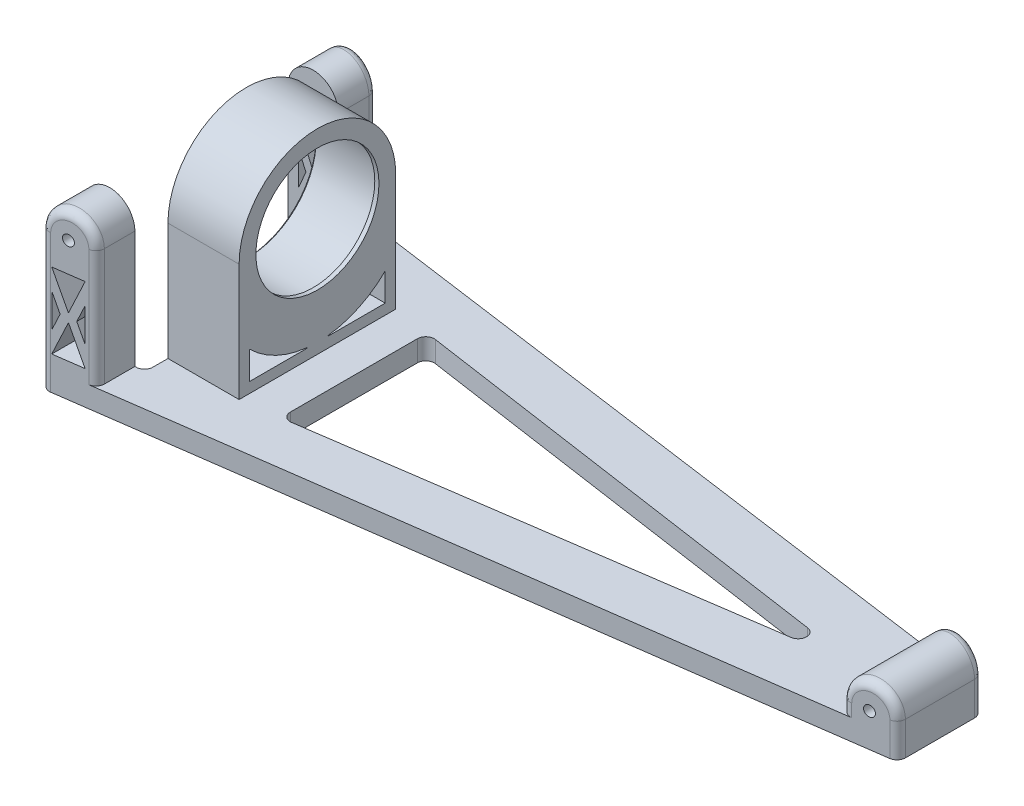
SolidWorks part; units mm, degrees
ref_plane "Front Plane" through (0, 0, 0) normal (0, 0, 1) x (1, 0, 0)
ref_plane "Top Plane" through (0, 0, 0) normal (0, 1, 0) x (1, 0, 0)
ref_plane "Right Plane" through (0, 0, 0) normal (1, 0, 0) x (0, 0, -1)
sketch "Sketch1" plane through (0, 0, 0) normal (0, 1, 0) x (1, 0, 0)
  line L0 (0, -35) -> (0, 35)
  line L13 (180, -10) -> (180, 10)
  line L14 (0, -35) -> (180, -10)
  line L19 (180, 10) -> (0, 35)
  point P3 (0, 0)
  point P6 (180, 0)
  dimension "D1" = 20
  dimension "D2" = 70
  dimension "D3" = 180
extrude "Boss-Extrude1" add sketch "Sketch1" along normal blind 5 contours L19 | L19 region at (73.3333, 0, 0)
sketch "Sketch2" plane through (0, 0, 0) normal (0, 0, 1) x (1, 0, 0)
  line L0 (0, 5) -> (180, 5) construction
  line L1 (0, 5) -> (180, 5)
  line L2 (0, 5) -> (0, 33)
  line L3 (12, 5) -> (12, 33)
  line L4 (180, 5) -> (180, 8)
  line L5 (168, 5) -> (168, 8)
  line L6 (2.5, 26) -> (9.5, 26)
  line L7 (9.5, 26) -> (6, 18)
  line L8 (6, 18) -> (2.5, 26)
  line L9 (6, 16) -> (2.5, 8)
  line L10 (2.5, 8) -> (9.5, 8)
  line L11 (9.5, 8) -> (6, 16)
  line L12 (2.5, 21.0102) -> (2.5, 12.9898)
  line L13 (2.5, 12.9898) -> (4.2545, 17)
  line L14 (4.2545, 17) -> (2.5, 21.0102)
  line L15 (9.5, 21.0102) -> (9.5, 12.9898)
  line L16 (9.5, 12.9898) -> (7.7455, 17)
  line L17 (7.7455, 17) -> (9.5, 21.0102)
  line L18 (6, 18) -> (6, 16) construction
  arc A0 (0, 33) -> (12, 33) centre (6, 33) cw
  circle A2 centre (174, 8) radius 1.25
  arc A3 (168, 8) -> (180, 8) centre (174, 8) cw
  circle A4 centre (6, 33) radius 1.25
  point P26 (6, 17)
  dimension "D1" = 28
  dimension "D2" = 6
  dimension "D4" = 3
  dimension "D3" = 2.5
  dimension "D5" = 18
  dimension "D6" = 3
  dimension "D7" = 8
  dimension "D8" = 7
  dimension "D9" = 2
extrude "Boss-Extrude2" add sketch "Sketch2" along normal up to surface and the other way up to surface contours L2 L1 | L1 A2 region at (0.3606, 19, 0) region at (168.15, 6.5, 0) up to face at (90, 2.5, 22.5) other way up to face at (90, 2.5, -22.5)
sketch "Sketch4" plane through (0, 0, 0) normal (0, 1, 0) x (1, 0, 0)
  line L1 (0, 24.3) -> (14.3, 24.3)
  line L2 (0, 24.3) -> (0, -24.3)
  line L3 (0, -24.3) -> (14.3, -24.3)
  line L4 (14.3, 24.3) -> (14.3, -24.3)
  line L5 (0, -35) -> (0, 35) construction
  point P6 (14.3, 0)
  dimension "D1" = 48.6
  dimension "D2" = 14.3
extrude "Cut-Extrude1" cut sketch "Sketch4" along normal through all both and the other way through all
sketch "Sketch5" plane through (14.3, 0, 0) normal (-1, 0, 0) x (0, 0, 1)
  line L0 (-18.7, 5) -> (-18.7, 33)
  line L1 (-24.3, 5) -> (24.3, 5) construction
  line L2 (18.7, 5) -> (18.7, 33)
  line L3 (18.7, 5) -> (-18.7, 5)
  line L7 (16.2, 7.5) -> (16.2, 14.1733)
  line L8 (16.2, 7.5) -> (2.5, 7.5)
  line L9 (-16.2, 7.5) -> (-16.2, 14.1733)
  line L10 (-16.2, 7.5) -> (-16.2, 33) construction
  line L11 (16.2, 7.5) -> (16.2, 33) construction
  line L12 (-2.5, 7.6363) -> (-2.5, 7.5)
  line L13 (-2.5, 7.5) -> (-16.2, 7.5)
  line L14 (2.5, 7.6363) -> (2.5, 7.5)
  line L15 (16.2, 7.5) -> (-16.2, 7.5) construction
  arc A0 (-18.7, 33) -> (18.7, 33) centre (0, 33) cw
  circle A1 centre (0, 33) radius 16.2
  arc A3 (-16.2, 14.1733) -> (-2.5, 7.6363) centre (0, 30.5) ccw
  arc A4 (2.5, 7.6363) -> (16.2, 14.1733) centre (0, 30.5) ccw
  ellipse E1 centre (-34.1667, 33) end of major axis (-34.1667, 34.25) minor radius 0.1736 construction
  ellipse E2 centre (-34.1667, 33) end of major axis (-34.1667, 34.25) minor radius 0.1736
  point P6 (0, 5)
  point P29 (2.5, 7.5681)
  line M9 (24.3, 5) -> (-24.3, 5)
  dimension "D3" = 32.4
  dimension "D2" = 2.5
  dimension "D1" = 2.5
  dimension "D4" = 2.5
  dimension "D5" = 5
extrude "Boss-Extrude3" add sketch "Sketch5" against normal blind 16.5 contours A1 L2 A0 L0 M9 region at (14.3, 19, -18.1017)
sketch "Sketch7" plane through (30.8, 0, 0) normal (1, 0, 0) x (0, 0, -1)
  line L9 (-18.7, 33) -> (-18.7, 5)
  line L10 (-18.7, 5) -> (18.7, 5)
  line L11 (18.7, 5) -> (18.7, 33)
  line L12 (-18.7, 33) -> (-18.7, 5)
  line L13 (-18.7, 5) -> (18.7, 5)
  line L14 (18.7, 5) -> (18.7, 33)
  arc A3 (18.7, 33) -> (-18.7, 33) centre (0, 33) ccw
  arc A4 (18.7, 33) -> (-18.7, 33) centre (0, 33) ccw
  circle A7 centre (0, 33) radius 14.7
  circle A8 centre (0, 33) radius 14.7
  circle M6 centre (0, 33) radius 16.2
  arc M7 (18.7, 33) -> (-18.7, 33) centre (0, 33) ccw
  line M8 (-18.7, 33) -> (-18.7, 5)
  line M10 (18.7, 5) -> (18.7, 33)
  line M12 (-18.7, 5) -> (18.7, 5)
  line M15 (16.2, 14.1733) -> (16.2, 7.5)
  line M16 (-2.5, 7.5) -> (-16.2, 7.5)
  line M17 (-16.2, 7.5) -> (-16.2, 14.1733)
  line M18 (16.2, 7.5) -> (2.5, 7.5)
  line M19 (2.5, 7.5) -> (2.5, 7.6363)
  arc M20 (2.5, 7.6363) -> (16.2, 14.1733) centre (0, 30.5) ccw
  line M21 (-2.5, 7.6363) -> (-2.5, 7.5)
  arc M22 (-16.2, 14.1733) -> (-2.5, 7.6363) centre (0, 30.5) ccw
  dimension "D1" = 0
  dimension "D2" = 1.5
extrude "Boss-Extrude5" add sketch "Sketch7" along normal mid plane 1 contours M10 M7 M8 M12 M22 M21 M16 M17 M20 M15 M18 M19 M6 | A8 M6 region at (30.8, 51.1017, 0) region at (30.8, 33, 15.7418)
sketch "Sketch8" plane through (0, 5, 0) normal (0, 1, 0) x (1, 0, 0)
  line L0 (40, 17.5) -> (40, -17.5)
  line L1 (40, -17.5) -> (160, 0)
  line L2 (160, 0) -> (40, 17.5)
  point P4 (40, 0)
  dimension "D1" = 40
  dimension "D2" = 120
  dimension "D3" = 35
extrude "Cut-Extrude2" cut sketch "Sketch8" against normal through all
fillet "Fillet2" radius 2 3 edges at (160, 2.5, 0) (40, 2.5, 17.5) (40, 2.5, -17.5)
fillet "Fillet5" radius 2 2 edges at (14.3, 2.5, 24.3) (14.3, 2.5, -24.3)
chamfer "Chamfer1" distance 0.5 angle 45 1 edges at (14.3, 33, 16.2)
fillet "Fillet6" radius 2 12 edges at (180, 4, -10) (168, 6.5, -11.6667) (180, 4, 10) (168, 6.5, 11.6667) (12, 19, -33.3333) (0, 16.5, -35) (12, 19, 33.3333) (0, 16.5, 35) (174, 14, -10.8333) (174, 14, 10.8333) (6, 39, -34.1667) (6, 39, 34.1667)
